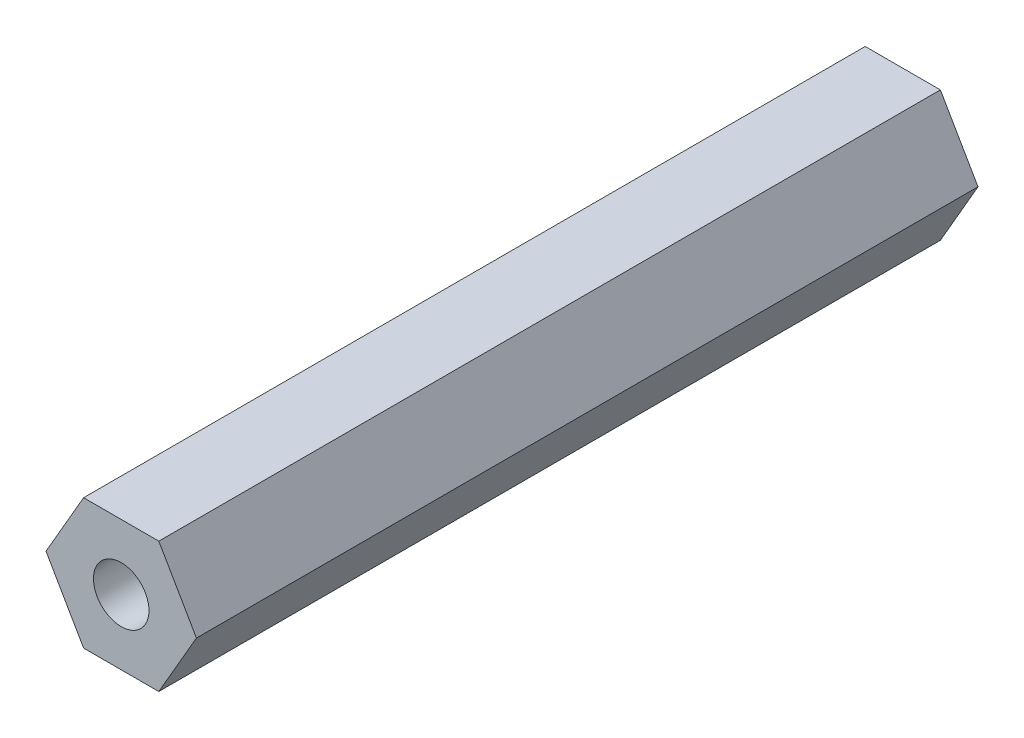
SolidWorks part; units mm, degrees
ref_plane "Front Plane" through (0, 0, 0) normal (0, 0, 1) x (1, 0, 0)
ref_plane "Top Plane" through (0, 0, 0) normal (0, 1, 0) x (1, 0, 0)
ref_plane "Right Plane" through (0, 0, 0) normal (1, 0, 0) x (0, 0, -1)
sketch "Sketch1" plane through (0, 0, 0) normal (0, 0, 1) x (1, 0, 0)
  line L1 (7.3323, 0) -> (3.6662, 6.35)
  line L2 (3.6662, 6.35) -> (-3.6662, 6.35)
  line L3 (-3.6662, 6.35) -> (-7.3323, 0)
  line L4 (-7.3323, 0) -> (-3.6662, -6.35)
  line L5 (-3.6662, -6.35) -> (3.6662, -6.35)
  line L6 (3.6662, -6.35) -> (7.3323, 0)
  circle A0 centre (0, 0) radius 6.35 construction
  dimension "D1" = 12.7
extrude "Boss-Extrude1" add sketch "Sketch1" along normal mid plane 76.2
hole_wizard "1/4-28 Tapped Hole1" positions "Sketch3" profile "Sketch2" tap size "1/4-28" standard "ANSI Inch"
sketch "Sketch3" plane through (0, 0, 38.1) normal (0, 0, 1) x (1, 0, 0)
  point P0 (0, 0)
sketch "Sketch2" plane through (0, 0, 38.1) normal (1, 0, 0) x (0, -1, 0)
  line L0 (0, 0) -> (0, 23.8504)
  line L1 (0, 23.8504) -> (2.7051, 22.225)
  line L2 (2.7051, 22.225) -> (2.7051, 0)
  line L5 (2.7051, 0) -> (0, 0)
  line L10 (0, 23.8504) -> (-2.7051, 22.225) construction
  line L11 (0, -6.35) -> (0, 107.95) construction
  dimension "Tap Drill Dia." = 5.4102
  dimension "Tap Drill Depth" = 22.225
  dimension "Drill Angle" = 118
hole_wizard "1/4-28 Tapped Hole2" positions "Sketch5" profile "Sketch4" tap size "1/4-28" standard "ANSI Inch"
sketch "Sketch5" plane through (0, 0, -38.1) normal (0, 0, -1) x (-1, 0, 0)
  point P0 (0, 0)
sketch "Sketch4" plane through (0, 0, -38.1) normal (1, 0, 0) x (0, 1, 0)
  line L0 (0, 0) -> (0, 23.8504)
  line L1 (0, 23.8504) -> (2.7051, 22.225)
  line L2 (2.7051, 22.225) -> (2.7051, 0)
  line L5 (2.7051, 0) -> (0, 0)
  line L10 (0, 23.8504) -> (-2.7051, 22.225) construction
  line L11 (0, -6.35) -> (0, 107.95) construction
  dimension "Tap Drill Dia." = 5.4102
  dimension "Tap Drill Depth" = 22.225
  dimension "Drill Angle" = 118
